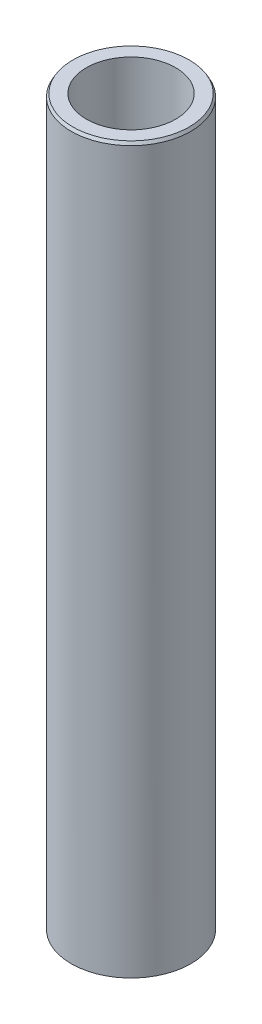
SolidWorks part; units mm, degrees
ref_plane "Front Plane" through (0, 0, 0) normal (0, 0, 1) x (1, 0, 0)
ref_plane "Top Plane" through (0, 0, 0) normal (0, 1, 0) x (1, 0, 0)
ref_plane "Right Plane" through (0, 0, 0) normal (1, 0, 0) x (0, 0, -1)
sketch "Sketch1" plane through (0, 0, 0) normal (0, 1, 0) x (1, 0, 0)
  circle A0 centre (0, 0) radius 27.5
  dimension "SHAFT_OD" = 55
extrude "Boss-Extrude1" add sketch "Sketch1" along normal blind 333.3717
sketch "Sketch2" plane through (0, 0, 0) normal (0, 1, 0) x (1, 0, 0)
  circle A0 centre (0, 0) radius 20.5275
  dimension "BORE_D" = 41.0551
extrude "Cut-Extrude1" cut sketch "Sketch2" along normal through all
chamfer "Chamfer1" distance 1.3537 angle 30 2 edges at (0, 333.3717, 27.5) (0, 0, 27.5) first distance on face at (0, 333.3717, 27.5) first distance on face at (0, 0, 20.5275)
